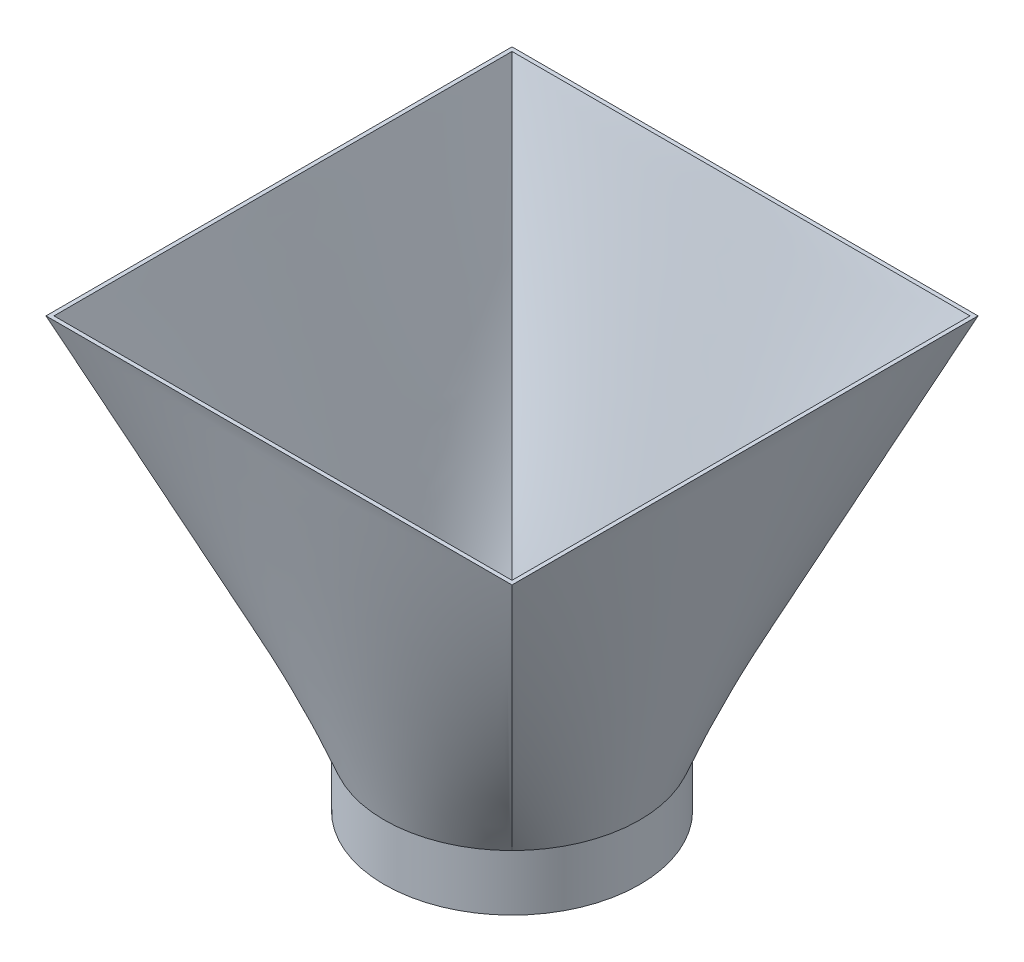
SolidWorks part; units mm, degrees
ref_plane "Front Plane" through (0, 0, 0) normal (0, 0, 1) x (1, 0, 0)
ref_plane "Top Plane" through (0, 0, 0) normal (0, 1, 0) x (1, 0, 0)
ref_plane "Right Plane" through (0, 0, 0) normal (1, 0, 0) x (0, 0, -1)
sketch "Sketch1" plane through (0, 0, 0) normal (0, 1, 0) x (1, 0, 0)
  circle A0 centre (0, 0) radius 68.5
  dimension "D1" = 137
ref_plane "Plane1" through (0, 200, 0) normal (0, 1, 0) x (1, 0, 0)
sketch "Sketch3" plane through (0, 200, 0) normal (0, 1, 0) x (1, 0, 0)
  line L1 (-125, -125) -> (125, -125)
  line L2 (-125, -125) -> (-125, 125)
  line L3 (-125, 125) -> (125, 125)
  line L4 (125, -125) -> (125, 125)
  line L5 (-125, -125) -> (125, 125) construction
  line L6 (-125, 125) -> (125, -125) construction
  point P0 (0, 0)
  dimension "D1" = 250
loft "Loft1" add profiles "Sketch3", "Sketch1" connector at (125, 200, -125) connector at (68.4946, 0, -0.8608)
shell "Shell1" thickness 2 removed face at (0, 200, 0) removed face at (0, 0, 0)
sketch "Sketch4" plane through (0, 0, 0) normal (0, -1, 0) x (1, 0, 0)
  circle A0 centre (0, 0) radius 68.5
  circle A1 centre (0, 0) radius 66.5
  dimension "D1" = 137
  dimension "D2" = 2
extrude "Boss-Extrude1" add sketch "Sketch4" along normal blind 30
